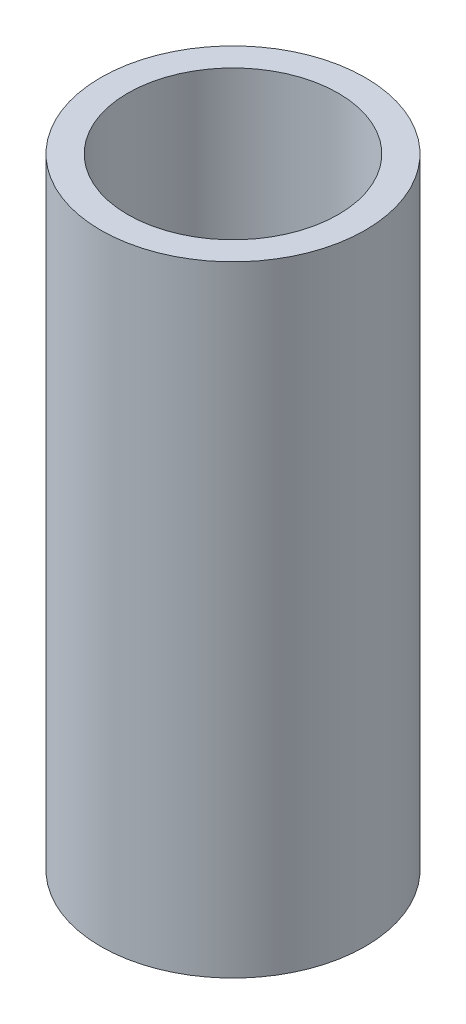
SolidWorks part; units mm, degrees
ref_plane "Front Plane" through (0, 0, 0) normal (0, 0, 1) x (1, 0, 0)
ref_plane "Top Plane" through (0, 0, 0) normal (0, 1, 0) x (1, 0, 0)
ref_plane "Right Plane" through (0, 0, 0) normal (1, 0, 0) x (0, 0, -1)
sketch "Sketch1" plane through (0, 0, 0) normal (0, 1, 0) x (1, 0, 0)
  circle A0 centre (0, 0) radius 20
  dimension "SLEEVE_OD" = 40
extrude "Boss-Extrude1" add sketch "Sketch1" along normal blind 93.8158
sketch "Sketch2" plane through (0, 0, 0) normal (0, 1, 0) x (1, 0, 0)
  circle A0 centre (0, 0) radius 15.9182
  dimension "BORE_D" = 31.8364
extrude "Cut-Extrude1" cut sketch "Sketch2" along normal through all
chamfer "Chamfer1" distance 2.4379 angle 41.5 rebuild error yes
